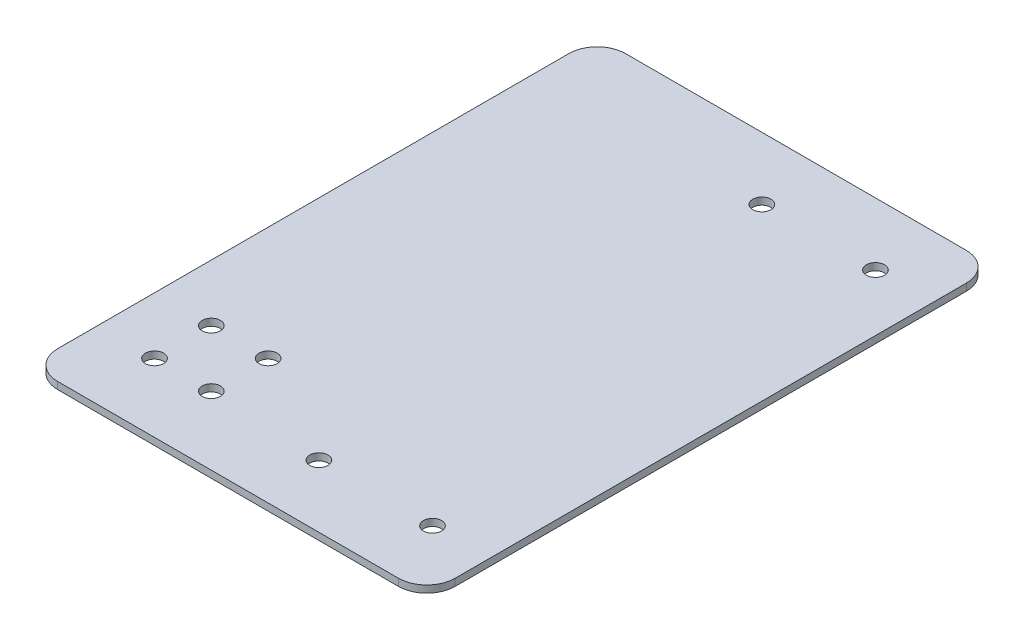
SolidWorks part; units mm, degrees
ref_plane "Front Plane" through (0, 0, 0) normal (0, 0, 1) x (1, 0, 0)
ref_plane "Top Plane" through (0, 0, 0) normal (0, 1, 0) x (1, 0, 0)
ref_plane "Right Plane" through (0, 0, 0) normal (1, 0, 0) x (0, 0, -1)
sketch "Sketch1" plane through (0, 0, 0) normal (0, 1, 0) x (1, 0, 0)
  line L0 (120.65, -35.4965) -> (57.15, -35.4965) construction
  line L1 (-120.65, 63.5) -> (120.65, 63.5)
  line L2 (-120.65, 63.5) -> (-120.65, -63.5)
  line L3 (-120.65, -63.5) -> (120.65, -63.5)
  line L4 (120.65, 63.5) -> (120.65, -63.5)
  line L5 (-120.65, 63.5) -> (120.65, -63.5) construction
  line L6 (-120.65, -63.5) -> (120.65, 63.5) construction
  line L7 (120.65, -49.53) -> (107.95, -49.53) construction
  line L8 (107.95, -49.53) -> (82.55, -49.53) construction
  line L9 (120.65, 49.53) -> (107.95, 49.53) construction
  line L10 (107.95, 49.53) -> (82.55, 49.53) construction
  line L11 (57.15, -35.4965) -> (44.45, -35.4965) construction
  line L12 (44.45, -35.4965) -> (44.45, -48.1965) construction
  line L13 (44.45, -48.1965) -> (57.15, -48.1965) construction
  line L14 (57.15, -48.1965) -> (57.15, -35.4965) construction
  circle A0 centre (82.55, 49.53) radius 2.032
  circle A1 centre (82.55, -49.53) radius 2.032
  circle A2 centre (107.95, -49.53) radius 2.032
  circle A3 centre (107.95, 49.53) radius 2.032
  circle A4 centre (57.15, -35.4965) radius 2.032
  circle A5 centre (44.45, -35.4965) radius 2.032
  circle A6 centre (44.45, -48.1965) radius 2.032
  circle A7 centre (57.15, -48.1965) radius 2.032
  point P0 (0, 0)
  dimension "D7" = 4.064
  dimension "D1" = 241.3
  dimension "D2" = 127
  dimension "D3" = 12.7
  dimension "D4" = 25.4
  dimension "D5" = 13.97
  dimension "D6" = 13.97
  dimension "D8" = 63.5
  dimension "D9" = 12.7
  dimension "D10" = 28.0035
  dimension "D11" = 12.7
extrude "Boss-Extrude1" add sketch "Sketch1" along normal blind 1.5875 contours L1 L3 L4 A7 A6 A5 A4 A3 A2 A1 A0 region at (-0.2481, 0, -0.0711)
sketch "Sketch2" plane through (0, 1.5875, 0) normal (0, 1, 0) x (1, 0, 0)
  line L0 (31.75, 63.5) -> (31.75, -63.5)
  line L1 (-120.65, 63.5) -> (120.65, 63.5) construction
  line L2 (-120.65, -63.5) -> (120.65, -63.5) construction
  circle A0 centre (44.45, -48.1965) radius 2.032 construction
  line M11 (120.65, 63.5) -> (-120.65, 63.5)
  line M12 (-120.65, 63.5) -> (-120.65, -63.5)
  line M13 (-120.65, -63.5) -> (120.65, -63.5)
  dimension "D1" = 12.7
extrude "Cut-Extrude1" cut sketch "Sketch2" against normal through all contours L0 M11 M12 M13 region at (-44.45, 1.5875, 0)
fillet "Fillet1" [suppressed] radius 6.35
fillet "Fillet2" radius 6.35 4 edges at (120.65, 0.7937, -63.5) (120.65, 0.7937, 63.5) (31.75, 0.7937, -63.5) (31.75, 0.7937, 63.5)
